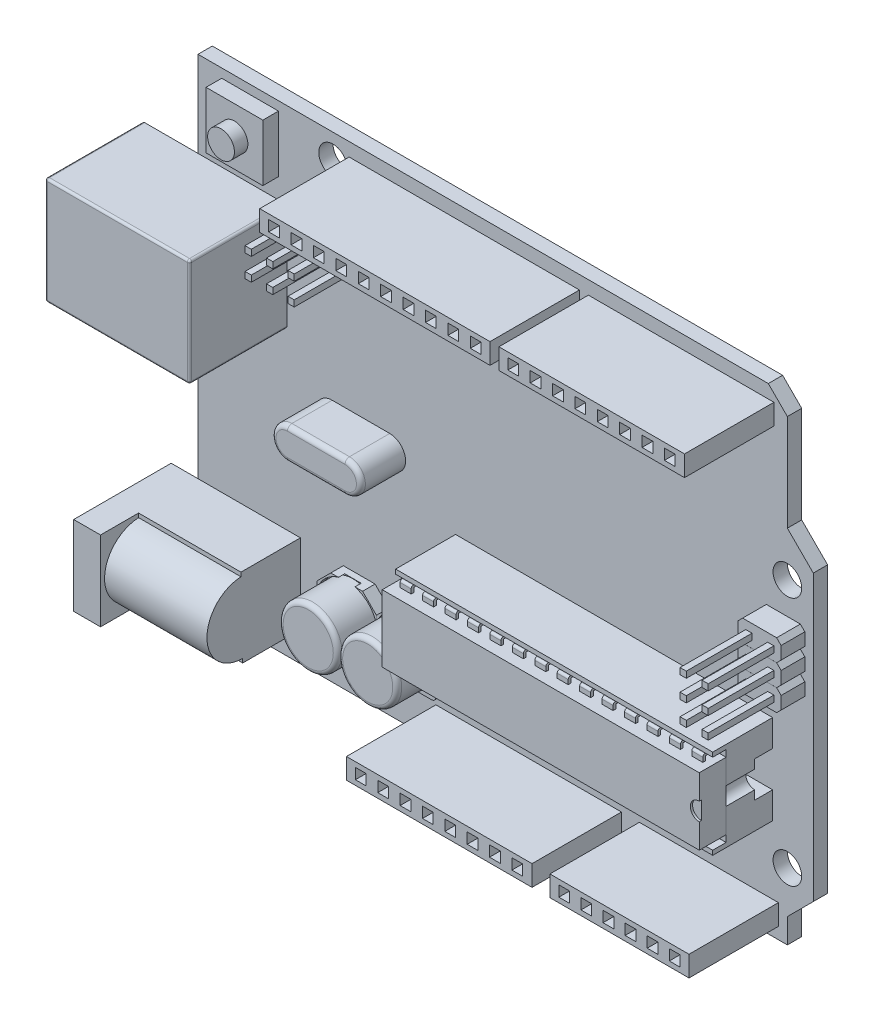
SolidWorks part; units mm, degrees
ref_plane "Plan de face" through (0, 0, 0) normal (0, 0, 1) x (1, 0, 0)
ref_plane "Plan de dessus" through (0, 0, 0) normal (0, 1, 0) x (1, 0, 0)
ref_plane "Plan de droite" through (0, 0, 0) normal (1, 0, 0) x (0, 0, -1)
sketch "Esquisse1" plane through (0, 0, 0) normal (0, 0, 1) x (1, 0, 0)
  line L0 (0, 0) -> (0, 53.3)
  line L1 (0, 53.3) -> (63.7689, 53.3)
  line L2 (63.7689, 53.3) -> (65.9, 51.1689)
  line L3 (68.8, 37.4589) -> (68.8, 5.65)
  line L4 (68.8, 5.65) -> (65.9, 2.75)
  line L5 (65.9, 2.75) -> (65.9, 0)
  line L6 (65.9, 0) -> (0, 0)
  line L7 (65.9, 51.1689) -> (65.9, 40.3589)
  line L8 (65.9, 40.3589) -> (68.8, 37.4589)
  circle A0 centre (14, 2.75) radius 1.6
  circle A1 centre (15.1, 50.55) radius 1.6
  circle A2 centre (65.9, 7.45) radius 1.6
  circle A3 centre (65.9, 35.35) radius 1.6
  dimension "D3" = 3.2
  dimension "D12" = 50.8
  dimension "D7" = 51.9
  dimension "D1" = 53.3
  dimension "D2" = 68.8
  dimension "D4" = 15.2
  dimension "D5" = 14
  dimension "D6" = 2.75
  dimension "D8" = 51.9
  dimension "D9" = 1.1
  dimension "D10" = 4.7
  dimension "D11" = 2.75
  dimension "D13" = 45
  dimension "D14" = 45
  dimension "D16" = 45
extrude "Boss.-Extru.1" add sketch "Esquisse1" along normal blind 1.6
sketch "Esquisse2" plane through (0, 0, 1.6) normal (0, 0, 1) x (1, 0, 0)
  line L0 (-6.2, 43.7) -> (9.95, 43.7)
  line L2 (9.95, 43.7) -> (9.95, 31.7)
  line L3 (9.95, 31.7) -> (-6.2, 31.7)
  line L4 (-6.2, 31.7) -> (-6.2, 43.7)
  line L5 (63.7689, 53.3) -> (0, 53.3) construction
  line L6 (68.8, 5.65) -> (68.8, 37.4589) construction
  dimension "D1" = 9.6
  dimension "D2" = 12
  dimension "D3" = 75
  dimension "D4" = 16.15
extrude "Boss.-Extru.2" add sketch "Esquisse2" along normal blind 10.9 separate body
sketch "Esquisse3" plane through (0, 0, 1.6) normal (0, 0, 1) x (1, 0, 0)
  line L0 (0, 53.3) -> (0, 0) construction
  line L1 (-3, 12.2) -> (11.45, 12.2)
  line L2 (-3, 12.2) -> (-3, 3.3)
  line L3 (-3, 3.3) -> (11.45, 3.3)
  line L4 (11.45, 12.2) -> (11.45, 3.3)
  line L5 (0, 0) -> (65.9, 0) construction
  dimension "D1" = 3
  dimension "D2" = 8.9
  dimension "D3" = 3.3
  dimension "D4" = 14.45
extrude "Boss.-Extru.3" add sketch "Esquisse3" along normal blind 10.9 separate body
sketch "Esquisse4" plane through (0, 0, 1.6) normal (0, 0, 1) x (1, 0, 0)
  line L0 (0, 0) -> (65.9, 0) construction
  line L1 (64.9, 3.6) -> (49.35, 3.6)
  line L2 (64.9, 3.6) -> (64.9, 1.3)
  line L3 (64.9, 1.3) -> (49.35, 1.3)
  line L4 (49.35, 3.6) -> (49.35, 1.3)
  line L5 (50.35, 3.05) -> (51.55, 3.05)
  line L6 (50.35, 3.05) -> (50.35, 1.85)
  line L7 (50.35, 1.85) -> (51.55, 1.85)
  line L8 (51.55, 3.05) -> (51.55, 1.85)
  line L9 (65.9, 0) -> (65.9, 2.75) construction
  line L10 (52.82, 1.85) -> (54.02, 1.85)
  line L11 (54.02, 3.05) -> (54.02, 1.85)
  line L12 (52.82, 3.05) -> (54.02, 3.05)
  line L13 (52.82, 3.05) -> (52.82, 1.85)
  line L14 (55.29, 1.85) -> (56.49, 1.85)
  line L15 (56.49, 3.05) -> (56.49, 1.85)
  line L16 (55.29, 3.05) -> (56.49, 3.05)
  line L17 (55.29, 3.05) -> (55.29, 1.85)
  line L18 (57.76, 1.85) -> (58.96, 1.85)
  line L19 (58.96, 3.05) -> (58.96, 1.85)
  line L20 (57.76, 3.05) -> (58.96, 3.05)
  line L21 (57.76, 3.05) -> (57.76, 1.85)
  line L22 (60.23, 1.85) -> (61.43, 1.85)
  line L23 (61.43, 3.05) -> (61.43, 1.85)
  line L24 (60.23, 3.05) -> (61.43, 3.05)
  line L25 (60.23, 3.05) -> (60.23, 1.85)
  line L26 (62.7, 1.85) -> (63.9, 1.85)
  line L27 (63.9, 3.05) -> (63.9, 1.85)
  line L28 (62.7, 3.05) -> (63.9, 3.05)
  line L29 (62.7, 3.05) -> (62.7, 1.85)
  dimension "D1" = 1
  dimension "D2" = 2.3
  dimension "D3" = 1.3
  dimension "D4" = 1
  dimension "D5" = 1.2
  dimension "D6" = 0.55
  dimension "D7" = 1
  dimension "D9" = 15.55
  dimension "D8" = 6
extrude "Boss.-Extru.4" add sketch "Esquisse4" along normal blind 10 separate body
sketch "Esquisse5" plane through (11.45, 0, 0) normal (1, 0, 0) x (0, 0, -1)
  line L0 (-8.05, 3.7548) -> (-8.05, 3.3)
  line L1 (-12.5, 3.3) -> (-1.6, 3.3) construction
  line L2 (-12.5, 12.2) -> (-1.6, 12.2) construction
  line L3 (-12.5, 12.2) -> (-12.5, 3.3) construction
  line L4 (-8.05, 3.3) -> (-12.5, 3.3)
  line L5 (-12.5, 3.3) -> (-12.5, 12.2)
  line L6 (-12.5, 12.2) -> (-8.2459, 12.2)
  line L7 (-8.2459, 12.2) -> (-8.2459, 11.75)
  arc A0 (-8.2459, 11.75) -> (-8.05, 3.7548) centre (-8.05, 7.7548) ccw
  point P5 (-12.5, 7.75)
  dimension "D1" = 4
  dimension "D2" = 0.45
  dimension "D3" = 4.45
extrude "Enlèv. mat.-Extru.1" cut sketch "Esquisse5" against normal up to surface (11.45 mm away) up to face at (0, 26.65, 0.8)
sketch "Esquisse6" plane through (0, 0, 1.6) normal (0, 0, 1) x (1, 0, 0)
  line L0 (15, 25.525) -> (21.44, 25.525) construction
  line L1 (15, 27.3) -> (21.44, 27.3)
  line L2 (15, 23.75) -> (21.44, 23.75)
  line L4 (-6.2, 31.7) -> (9.95, 31.7) construction
  line L5 (0, 53.3) -> (0, 0) construction
  arc A0 (15, 27.3) -> (15, 23.75) centre (15, 25.525) ccw
  arc A1 (21.44, 23.75) -> (21.44, 27.3) centre (21.44, 25.525) ccw
  point P2 (18.22, 25.525)
  dimension "D1" = 1.775
  dimension "D2" = 6.44
  dimension "D3" = 15
  dimension "D4" = 4.4
extrude "Boss.-Extru.5" add sketch "Esquisse6" along normal blind 5 separate body
sketch "Esquisse8" plane through (0, 0, 1.6) normal (0, 0, 1) x (1, 0, 0)
  line L0 (64.9, 3.6) -> (49.35, 3.6) construction
  line L1 (47.35, 3.6) -> (26.6, 3.6)
  line L2 (47.35, 3.6) -> (47.35, 1.3)
  line L3 (47.35, 1.3) -> (26.6, 1.3)
  line L4 (26.6, 3.6) -> (26.6, 1.3)
  line L5 (49.35, 1.3) -> (64.9, 1.3) construction
  line L6 (49.35, 3.6) -> (49.35, 1.3) construction
  line L7 (51.55, 3.05) -> (50.35, 3.05) construction
  line L8 (27.6, 3.05) -> (28.8, 3.05)
  line L9 (27.6, 3.05) -> (27.6, 1.85)
  line L10 (27.6, 1.85) -> (28.8, 1.85)
  line L11 (28.8, 3.05) -> (28.8, 1.85)
  line L12 (50.35, 1.85) -> (51.55, 1.85) construction
  line L13 (30.1, 1.85) -> (31.3, 1.85)
  line L14 (31.3, 3.05) -> (31.3, 1.85)
  line L15 (30.1, 3.05) -> (31.3, 3.05)
  line L16 (30.1, 3.05) -> (30.1, 1.85)
  line L17 (32.6, 1.85) -> (33.8, 1.85)
  line L18 (33.8, 3.05) -> (33.8, 1.85)
  line L19 (32.6, 3.05) -> (33.8, 3.05)
  line L20 (32.6, 3.05) -> (32.6, 1.85)
  line L21 (35.1, 1.85) -> (36.3, 1.85)
  line L22 (36.3, 3.05) -> (36.3, 1.85)
  line L23 (35.1, 3.05) -> (36.3, 3.05)
  line L24 (35.1, 3.05) -> (35.1, 1.85)
  line L25 (37.6, 1.85) -> (38.8, 1.85)
  line L26 (38.8, 3.05) -> (38.8, 1.85)
  line L27 (37.6, 3.05) -> (38.8, 3.05)
  line L28 (37.6, 3.05) -> (37.6, 1.85)
  line L29 (40.1, 1.85) -> (41.3, 1.85)
  line L30 (41.3, 3.05) -> (41.3, 1.85)
  line L31 (40.1, 3.05) -> (41.3, 3.05)
  line L32 (40.1, 3.05) -> (40.1, 1.85)
  line L33 (42.6, 1.85) -> (43.8, 1.85)
  line L34 (43.8, 3.05) -> (43.8, 1.85)
  line L35 (42.6, 3.05) -> (43.8, 3.05)
  line L36 (42.6, 3.05) -> (42.6, 1.85)
  line L37 (45.1, 1.85) -> (46.3, 1.85)
  line L38 (46.3, 3.05) -> (46.3, 1.85)
  line L39 (45.1, 3.05) -> (46.3, 3.05)
  line L40 (45.1, 3.05) -> (45.1, 1.85)
  point P8 (49.35, 2.45)
  dimension "D1" = 2
  dimension "D2" = 20.75
  dimension "D3" = 1.2
  dimension "D4" = 1
  dimension "D5" = 8
extrude "Boss.-Extru.6" add sketch "Esquisse8" along normal blind 10 separate body
sketch "Esquisse9" plane through (0, 0, 1.6) normal (0, 0, 1) x (1, 0, 0)
  line L0 (14.7, 10.35) -> (14.7, 5.75)
  line L1 (15.2, 5.25) -> (20.85, 5.25)
  line L2 (21.35, 5.75) -> (21.35, 10.35)
  line L3 (21.35, 10.35) -> (19.8, 11.9)
  line L4 (19.8, 11.9) -> (16.25, 11.9)
  line L5 (16.25, 11.9) -> (14.7, 10.35)
  line L6 (11.45, 3.7548) -> (11.45, 11.75) construction
  line L7 (0, 0) -> (65.9, 0) construction
  arc A0 (20.85, 5.25) -> (21.35, 5.75) centre (20.85, 5.75) ccw
  arc A1 (14.7, 5.75) -> (15.2, 5.25) centre (15.2, 5.75) ccw
  dimension "D8" = 0.5
  dimension "D1" = 6.65
  dimension "D2" = 6.65
  dimension "D3" = 45
  dimension "D4" = 45
  dimension "D5" = 3.55
  dimension "D6" = 3.25
  dimension "D7" = 5.25
extrude "Boss.-Extru.7" add sketch "Esquisse9" along normal blind 1.4 separate body
sketch "Esquisse10" plane through (0, 0, 3) normal (0, 0, 1) x (1, 0, 0)
  circle A0 centre (18.025, 8.575) radius 3.45
  dimension "D1" = 6.9
extrude "Enlèv. mat.-Extru.8" cut sketch "Esquisse10" against normal blind 0.7
pattern_linear "Répétition linéaire1" count 2 spacing 6.65 along (1, 0, 0) of bodies 111
sketch "Esquisse11" plane through (0, 0, 2.3) normal (0, 0, 1) x (1, 0, 0)
  circle A0 centre (18.025, 8.575) radius 3.3
  arc A1 (17.1047, 11.9) -> (14.7, 9.4953) centre (18.025, 8.575) ccw construction
  dimension "D1" = 6.6
extrude "Boss.-Extru.8" add sketch "Esquisse11" along normal blind 5 separate body
pattern_linear "Répétition linéaire2" count 2 spacing 6.65 along (1, 0, 0) of "Boss.-Extru.8"
fillet "Congé1" radius 0.5 1 edges at (21.325, 8.575, 7.3)
fillet "Congé2" radius 0.5 1 edges at (27.975, 8.575, 7.3)
fillet "Congé3" radius 0.5 4 edges at (13.225, 25.525, 6.6) (18.22, 27.3, 6.6) (23.215, 25.525, 6.6) (18.22, 23.75, 6.6)
sketch "Esquisse12" plane through (0, 0, 1.6) normal (0, 0, 1) x (1, 0, 0)
  line L0 (63.55, 31.8) -> (67.35, 31.8)
  line L1 (67.35, 31.8) -> (67.85, 31.3)
  line L2 (67.85, 31.3) -> (67.85, 29.8833)
  line L3 (67.85, 29.8833) -> (67.35, 29.3833)
  line L4 (67.35, 29.3833) -> (63.55, 29.3833)
  line L5 (63.55, 29.3833) -> (63.05, 29.8833)
  line L6 (63.05, 29.8833) -> (63.05, 31.3)
  line L7 (63.05, 31.3) -> (63.55, 31.8)
  line L8 (68.8, 5.65) -> (68.8, 37.4589) construction
  line L9 (49.35, 1.3) -> (64.9, 1.3) construction
  dimension "D1" = 45
  dimension "D2" = 45
  dimension "D3" = 45
  dimension "D4" = 2.4167
  dimension "D5" = 4.8
  dimension "D6" = 0.5
  dimension "D7" = 5.75
  dimension "D8" = 30.5
extrude "Boss.-Extru.9" add sketch "Esquisse12" along normal blind 2.65 separate body
pattern_linear "Répétition linéaire3" count 3 spacing 2.42 along (0, -1, 0) of bodies 115
sketch "Esquisse13" plane through (0, 0, 1.6) normal (0, 0, 1) x (1, 0, 0)
  line L0 (14.4, 43.9) -> (14.4, 47.7)
  line L1 (14.4, 47.7) -> (14.9, 48.2)
  line L2 (14.9, 48.2) -> (16.3167, 48.2)
  line L3 (16.3167, 48.2) -> (16.8167, 47.7)
  line L4 (16.8167, 47.7) -> (16.8167, 43.9)
  line L5 (16.8167, 43.9) -> (16.3167, 43.4)
  line L6 (16.3167, 43.4) -> (14.9, 43.4)
  line L7 (14.9, 43.4) -> (14.4, 43.9)
  line L8 (65.9, 40.3589) -> (65.9, 51.1689) construction
  line L9 (63.7689, 53.3) -> (0, 53.3) construction
  dimension "D1" = 45
  dimension "D2" = 45
  dimension "D3" = 45
  dimension "D4" = 2.4167
  dimension "D5" = 4.8
  dimension "D6" = 0.5
  dimension "D7" = 51.5
  dimension "D8" = 9.9
extrude "Boss.-Extru.10" add sketch "Esquisse13" along normal up to surface (2.65 mm away) up to face at (65.45, 30.5917, 4.25)
pattern_linear "Répétition linéaire4" count 3 spacing 2.42 along (1, 0, 0) of "Boss.-Extru.10"
sketch "Esquisse14" plane through (0, 0, 1.6) normal (0, 0, 1) x (1, 0, 0)
  line L0 (63.7689, 53.3) -> (0, 53.3) construction
  line L1 (2.65, 52.3) -> (9, 52.3)
  line L2 (2.65, 52.3) -> (2.65, 45.95)
  line L3 (2.65, 45.95) -> (9, 45.95)
  line L4 (9, 52.3) -> (9, 45.95)
  line L5 (0, 53.3) -> (0, 0) construction
  dimension "D1" = 6.35
  dimension "D2" = 6.35
  dimension "D3" = 1
  dimension "D4" = 9
extrude "Boss.-Extru.11" add sketch "Esquisse14" along normal blind 1.75 separate body
sketch "Esquisse15" plane through (0, 0, 3.35) normal (0, 0, 1) x (1, 0, 0)
  circle A0 centre (5.825, 49.125) radius 1.5
  point P2 (5.825, 49.125)
  dimension "D1" = 3
extrude "Boss.-Extru.12" add sketch "Esquisse15" along normal blind 1.5 separate body
sketch "Esquisse16" plane through (0, 0, 4.25) normal (0, 0, 1) x (1, 0, 0)
  line L0 (63.05, 26.46) -> (63.05, 25.0433) construction
  line L1 (67.05, 25.4) -> (66.35, 25.4)
  line L2 (67.05, 25.4) -> (67.05, 26.1)
  line L3 (67.05, 26.1) -> (66.35, 26.1)
  line L4 (66.35, 25.4) -> (66.35, 26.1)
  line L6 (67.35, 26.96) -> (63.55, 26.96) construction
  line L9 (64.6, 25.4) -> (63.9, 25.4)
  line L10 (64.6, 25.4) -> (64.6, 26.1)
  line L11 (64.6, 26.1) -> (63.9, 26.1)
  line L12 (63.9, 25.4) -> (63.9, 26.1)
  line L13 (64.6, 27.7833) -> (63.9, 27.7833)
  line L14 (64.6, 27.7833) -> (64.6, 28.4833)
  line L15 (64.6, 28.4833) -> (63.9, 28.4833)
  line L16 (63.9, 27.7833) -> (63.9, 28.4833)
  line L17 (64.6, 30.1667) -> (63.9, 30.1667)
  line L18 (64.6, 30.1667) -> (64.6, 30.8667)
  line L19 (64.6, 30.8667) -> (63.9, 30.8667)
  line L20 (63.9, 30.1667) -> (63.9, 30.8667)
  line L21 (67.05, 27.7833) -> (66.35, 27.7833)
  line L22 (67.05, 27.7833) -> (67.05, 28.4833)
  line L23 (67.05, 28.4833) -> (66.35, 28.4833)
  line L24 (66.35, 27.7833) -> (66.35, 28.4833)
  line L25 (67.05, 30.1667) -> (66.35, 30.1667)
  line L26 (67.05, 30.1667) -> (67.05, 30.8667)
  line L27 (67.05, 30.8667) -> (66.35, 30.8667)
  line L28 (66.35, 30.1667) -> (66.35, 30.8667)
  dimension "D1" = 0.7
  dimension "D2" = 4
  dimension "D3" = 0.86
  dimension "D4" = 2
  dimension "D5" = 3
extrude "Boss.-Extru.13" add sketch "Esquisse16" along normal up to surface (7.35 mm away) separate body up to face at (60.83, 2.45, 11.6)
sketch "Esquisse17" plane through (0, 0, 4.25) normal (0, 0, 1) x (1, 0, 0)
  line L0 (14.4, 43.9) -> (14.4, 47.7) construction
  line L1 (15.96, 44.2) -> (15.26, 44.2)
  line L2 (15.96, 44.2) -> (15.96, 44.9)
  line L3 (15.96, 44.9) -> (15.26, 44.9)
  line L4 (15.26, 44.2) -> (15.26, 44.9)
  line L6 (14.9, 43.4) -> (16.3167, 43.4) construction
  line L9 (16.3167, 48.2) -> (14.9, 48.2) construction
  line L10 (15.96, 46.7) -> (15.26, 46.7)
  line L11 (15.96, 46.7) -> (15.96, 47.4)
  line L12 (15.96, 47.4) -> (15.26, 47.4)
  line L13 (15.26, 46.7) -> (15.26, 47.4)
  line L14 (18.36, 46.7) -> (17.66, 46.7)
  line L15 (18.36, 46.7) -> (18.36, 47.4)
  line L16 (18.36, 47.4) -> (17.66, 47.4)
  line L17 (17.66, 46.7) -> (17.66, 47.4)
  line L18 (18.36, 44.2) -> (17.66, 44.2)
  line L19 (18.36, 44.2) -> (18.36, 44.9)
  line L20 (18.36, 44.9) -> (17.66, 44.9)
  line L21 (17.66, 44.2) -> (17.66, 44.9)
  line L22 (20.76, 46.7) -> (20.06, 46.7)
  line L23 (20.76, 46.7) -> (20.76, 47.4)
  line L24 (20.76, 47.4) -> (20.06, 47.4)
  line L25 (20.06, 46.7) -> (20.06, 47.4)
  line L26 (20.76, 44.2) -> (20.06, 44.2)
  line L27 (20.76, 44.2) -> (20.76, 44.9)
  line L28 (20.76, 44.9) -> (20.06, 44.9)
  line L29 (20.06, 44.2) -> (20.06, 44.9)
  point P21 (35.61, 45.8)
  dimension "D1" = 0.7
  dimension "D2" = 0.86
  dimension "D3" = 0.8
  dimension "D4" = 0.8
  dimension "D5" = 0.7
  dimension "D6" = 3
extrude "Boss.-Extru.14" add sketch "Esquisse17" along normal up to surface (7.35 mm away) separate body up to face at (43.2, 2.45, 11.6)
sketch "Esquisse19" plane through (0, 0, 1.6) normal (0, 0, 1) x (1, 0, 0)
  line L0 (64.4, 51.8) -> (43.65, 51.8)
  line L1 (64.4, 51.8) -> (64.4, 49.5)
  line L2 (64.4, 49.5) -> (43.65, 49.5)
  line L3 (43.65, 51.8) -> (43.65, 49.5)
  line L4 (44.65, 51.25) -> (45.85, 51.25)
  line L5 (44.65, 51.25) -> (44.65, 50.05)
  line L6 (44.65, 50.05) -> (45.85, 50.05)
  line L7 (45.85, 51.25) -> (45.85, 50.05)
  line L8 (47.15, 50.05) -> (48.35, 50.05)
  line L9 (48.35, 51.25) -> (48.35, 50.05)
  line L10 (47.15, 51.25) -> (48.35, 51.25)
  line L11 (47.15, 51.25) -> (47.15, 50.05)
  line L12 (49.65, 50.05) -> (50.85, 50.05)
  line L13 (50.85, 51.25) -> (50.85, 50.05)
  line L14 (49.65, 51.25) -> (50.85, 51.25)
  line L15 (49.65, 51.25) -> (49.65, 50.05)
  line L16 (52.15, 50.05) -> (53.35, 50.05)
  line L17 (53.35, 51.25) -> (53.35, 50.05)
  line L18 (52.15, 51.25) -> (53.35, 51.25)
  line L19 (52.15, 51.25) -> (52.15, 50.05)
  line L20 (54.65, 50.05) -> (55.85, 50.05)
  line L21 (55.85, 51.25) -> (55.85, 50.05)
  line L22 (54.65, 51.25) -> (55.85, 51.25)
  line L23 (54.65, 51.25) -> (54.65, 50.05)
  line L24 (57.15, 50.05) -> (58.35, 50.05)
  line L25 (58.35, 51.25) -> (58.35, 50.05)
  line L26 (57.15, 51.25) -> (58.35, 51.25)
  line L27 (57.15, 51.25) -> (57.15, 50.05)
  line L28 (59.65, 50.05) -> (60.85, 50.05)
  line L29 (60.85, 51.25) -> (60.85, 50.05)
  line L30 (59.65, 51.25) -> (60.85, 51.25)
  line L31 (59.65, 51.25) -> (59.65, 50.05)
  line L32 (62.15, 50.05) -> (63.35, 50.05)
  line L33 (63.35, 51.25) -> (63.35, 50.05)
  line L34 (62.15, 51.25) -> (63.35, 51.25)
  line L35 (62.15, 51.25) -> (62.15, 50.05)
  line L37 (65.9, 40.3589) -> (65.9, 51.1689) construction
  line L38 (63.7689, 53.3) -> (0, 53.3) construction
  dimension "D1" = 20.75
  dimension "D2" = 1.2
  dimension "D3" = 1
  dimension "D4" = 2.3
  dimension "D5" = 0.55
  dimension "D6" = 0.55
  dimension "D7" = 1.2
  dimension "D8" = 1.3
  dimension "D9" = 1.3
  dimension "D10" = 1.3
  dimension "D11" = 1.3
  dimension "D12" = 1.3
  dimension "D13" = 1.3
  dimension "D14" = 1.3
  dimension "D15" = 1.05
  dimension "D16" = 1.2
  dimension "D17" = 1.2
  dimension "D18" = 1.2
  dimension "D19" = 1.2
  dimension "D20" = 1.2
  dimension "D21" = 1.2
  dimension "D22" = 1.5
  dimension "D23" = 1.5
extrude "Boss.-Extru.15" add sketch "Esquisse19" along normal blind 10 separate body
sketch "Esquisse20" plane through (0, 0, 1.6) normal (0, 0, 1) x (1, 0, 0)
  line L0 (43.65, 49.5) -> (64.4, 49.5) construction
  line L1 (42.65, 49.5) -> (16.9, 49.5)
  line L2 (42.65, 49.5) -> (42.65, 51.8)
  line L3 (42.65, 51.8) -> (16.9, 51.8)
  line L4 (16.9, 49.5) -> (16.9, 51.8)
  line L5 (64.4, 51.8) -> (43.65, 51.8) construction
  line L6 (43.65, 51.8) -> (43.65, 49.5) construction
  line L7 (45.85, 51.25) -> (44.65, 51.25) construction
  line L8 (41.65, 50.05) -> (40.45, 50.05)
  line L9 (41.65, 50.05) -> (41.65, 51.25)
  line L10 (41.65, 51.25) -> (40.45, 51.25)
  line L11 (40.45, 50.05) -> (40.45, 51.25)
  line L12 (44.65, 50.05) -> (45.85, 50.05) construction
  line L13 (39.1444, 50.05) -> (37.9444, 50.05)
  line L14 (37.9444, 50.05) -> (37.9444, 51.25)
  line L15 (39.1444, 51.25) -> (37.9444, 51.25)
  line L16 (39.1444, 50.05) -> (39.1444, 51.25)
  line L17 (36.6389, 50.05) -> (35.4389, 50.05)
  line L18 (35.4389, 50.05) -> (35.4389, 51.25)
  line L19 (36.6389, 51.25) -> (35.4389, 51.25)
  line L20 (36.6389, 50.05) -> (36.6389, 51.25)
  line L21 (34.1333, 50.05) -> (32.9333, 50.05)
  line L22 (32.9333, 50.05) -> (32.9333, 51.25)
  line L23 (34.1333, 51.25) -> (32.9333, 51.25)
  line L24 (34.1333, 50.05) -> (34.1333, 51.25)
  line L25 (31.6278, 50.05) -> (30.4278, 50.05)
  line L26 (30.4278, 50.05) -> (30.4278, 51.25)
  line L27 (31.6278, 51.25) -> (30.4278, 51.25)
  line L28 (31.6278, 50.05) -> (31.6278, 51.25)
  line L29 (29.1222, 50.05) -> (27.9222, 50.05)
  line L30 (27.9222, 50.05) -> (27.9222, 51.25)
  line L31 (29.1222, 51.25) -> (27.9222, 51.25)
  line L32 (29.1222, 50.05) -> (29.1222, 51.25)
  line L33 (26.6167, 50.05) -> (25.4167, 50.05)
  line L34 (25.4167, 50.05) -> (25.4167, 51.25)
  line L35 (26.6167, 51.25) -> (25.4167, 51.25)
  line L36 (26.6167, 50.05) -> (26.6167, 51.25)
  line L37 (24.1111, 50.05) -> (22.9111, 50.05)
  line L38 (22.9111, 50.05) -> (22.9111, 51.25)
  line L39 (24.1111, 51.25) -> (22.9111, 51.25)
  line L40 (24.1111, 50.05) -> (24.1111, 51.25)
  line L41 (21.6056, 50.05) -> (20.4056, 50.05)
  line L42 (20.4056, 50.05) -> (20.4056, 51.25)
  line L43 (21.6056, 51.25) -> (20.4056, 51.25)
  line L44 (21.6056, 50.05) -> (21.6056, 51.25)
  line L45 (19.1, 50.05) -> (17.9, 50.05)
  line L46 (17.9, 50.05) -> (17.9, 51.25)
  line L47 (19.1, 51.25) -> (17.9, 51.25)
  line L48 (19.1, 50.05) -> (19.1, 51.25)
  dimension "D1" = 25.75
  dimension "D2" = 1
  dimension "D3" = 1.2
  dimension "D4" = 1
  dimension "D6" = 1
  dimension "D5" = 10
extrude "Boss.-Extru.16" add sketch "Esquisse20" along normal blind 10 separate body
sketch "Esquisse21" plane through (0, 0, 1.6) normal (0, 0, 1) x (1, 0, 0)
  line L0 (49.35, 1.3) -> (64.9, 1.3) construction
  line L1 (64.25, 11.2) -> (28.8, 11.2)
  line L2 (64.25, 11.2) -> (64.25, 15.2)
  line L3 (64.25, 21.2) -> (28.8, 21.2)
  line L4 (28.8, 11.2) -> (28.8, 21.2)
  line L5 (68.8, 5.65) -> (68.8, 37.4589) construction
  line L7 (64.25, 17.2) -> (64.25, 21.2)
  arc A0 (64.25, 15.2) -> (64.25, 17.2) centre (64.25, 16.2) cw
  dimension "D6" = 1
  dimension "D1" = 35.45
  dimension "D2" = 10
  dimension "D3" = 19.9
  dimension "D4" = 40
  dimension "D5" = 5
extrude "Boss.-Extru.17" add sketch "Esquisse21" along normal blind 6.7 separate body
sketch "Esquisse22" plane through (64.25, 0, 0) normal (1, 0, 0) x (0, 0, -1)
  line L0 (-1.6, 17.2) -> (-1.6, 21.2) construction
  line L1 (-3.6, 14.2) -> (-1.6, 14.2)
  line L2 (-3.6, 14.2) -> (-3.6, 18.2)
  line L3 (-3.6, 18.2) -> (-1.6, 18.2)
  line L4 (-1.6, 14.2) -> (-1.6, 18.2)
  line L5 (-8.3, 11.2) -> (-1.6, 11.2) construction
  line L6 (-8.3, 21.2) -> (-1.6, 21.2) construction
  line L7 (-8.3, 11.2) -> (-8.3, 15.2) construction
  line L8 (-8.3, 11.7) -> (-6.8, 11.7)
  line L9 (-8.3, 11.7) -> (-8.3, 20.7)
  line L10 (-8.3, 20.7) -> (-6.8, 20.7)
  line L11 (-6.8, 11.7) -> (-6.8, 20.7)
  dimension "D1" = 3
  dimension "D2" = 3
  dimension "D3" = 2
  dimension "D4" = 1.5
  dimension "D5" = 0.5
  dimension "D6" = 0.5
extrude "Enlèv. mat.-Extru.9" cut sketch "Esquisse22" against normal up to next
sketch "Esquisse23" plane through (0, 0, 6.8) normal (0, 0, 1) x (1, 0, 0)
  line L0 (28.8, 20.7) -> (28.8, 11.7) construction
  line L1 (28.8, 12.45) -> (64.25, 12.45)
  line L2 (28.8, 12.45) -> (28.8, 19.95)
  line L3 (28.8, 19.95) -> (64.25, 19.95)
  line L4 (64.25, 12.45) -> (64.25, 19.95)
  line L5 (64.25, 17.2) -> (64.25, 20.7) construction
  line L6 (28.8, 20.7) -> (64.25, 20.7) construction
  dimension "D1" = 0.75
  dimension "7.5" = 7.5
extrude "Boss.-Extru.18" add sketch "Esquisse23" along normal blind 3 separate body
sketch "Esquisse24" plane through (0, 0, 9.8) normal (0, 0, 1) x (1, 0, 0)
  line L0 (64.25, 19.95) -> (28.8, 19.95) construction
  line L1 (29.6, 19.95) -> (30.8322, 19.95)
  line L2 (29.6, 19.95) -> (29.6, 20.7)
  line L3 (29.6, 20.7) -> (30.8322, 20.7)
  line L4 (30.8322, 19.95) -> (30.8322, 20.7)
  line L5 (28.8, 20.7) -> (64.25, 20.7) construction
  line L6 (32.1091, 19.95) -> (33.3412, 19.95)
  line L7 (32.1091, 20.7) -> (33.3412, 20.7)
  line L8 (33.3412, 19.95) -> (33.3412, 20.7)
  line L9 (32.1091, 19.95) -> (32.1091, 20.7)
  line L10 (34.6181, 19.95) -> (35.8503, 19.95)
  line L11 (34.6181, 20.7) -> (35.8503, 20.7)
  line L12 (35.8503, 19.95) -> (35.8503, 20.7)
  line L13 (34.6181, 19.95) -> (34.6181, 20.7)
  line L14 (37.1272, 19.95) -> (38.3593, 19.95)
  line L15 (37.1272, 20.7) -> (38.3593, 20.7)
  line L16 (38.3593, 19.95) -> (38.3593, 20.7)
  line L17 (37.1272, 19.95) -> (37.1272, 20.7)
  line L18 (39.6363, 19.95) -> (40.8684, 19.95)
  line L19 (39.6363, 20.7) -> (40.8684, 20.7)
  line L20 (40.8684, 19.95) -> (40.8684, 20.7)
  line L21 (39.6363, 19.95) -> (39.6363, 20.7)
  line L22 (42.1453, 19.95) -> (43.3775, 19.95)
  line L23 (42.1453, 20.7) -> (43.3775, 20.7)
  line L24 (43.3775, 19.95) -> (43.3775, 20.7)
  line L25 (42.1453, 19.95) -> (42.1453, 20.7)
  line L26 (44.6544, 19.95) -> (45.8865, 19.95)
  line L27 (44.6544, 20.7) -> (45.8865, 20.7)
  line L28 (45.8865, 19.95) -> (45.8865, 20.7)
  line L29 (44.6544, 19.95) -> (44.6544, 20.7)
  line L30 (47.1635, 19.95) -> (48.3956, 19.95)
  line L31 (47.1635, 20.7) -> (48.3956, 20.7)
  line L32 (48.3956, 19.95) -> (48.3956, 20.7)
  line L33 (47.1635, 19.95) -> (47.1635, 20.7)
  line L34 (49.6725, 19.95) -> (50.9047, 19.95)
  line L35 (49.6725, 20.7) -> (50.9047, 20.7)
  line L36 (50.9047, 19.95) -> (50.9047, 20.7)
  line L37 (49.6725, 19.95) -> (49.6725, 20.7)
  line L38 (52.1816, 19.95) -> (53.4137, 19.95)
  line L39 (52.1816, 20.7) -> (53.4137, 20.7)
  line L40 (53.4137, 19.95) -> (53.4137, 20.7)
  line L41 (52.1816, 19.95) -> (52.1816, 20.7)
  line L42 (54.6907, 19.95) -> (55.9228, 19.95)
  line L43 (54.6907, 20.7) -> (55.9228, 20.7)
  line L44 (55.9228, 19.95) -> (55.9228, 20.7)
  line L45 (54.6907, 19.95) -> (54.6907, 20.7)
  line L46 (57.1997, 19.95) -> (58.4319, 19.95)
  line L47 (57.1997, 20.7) -> (58.4319, 20.7)
  line L48 (58.4319, 19.95) -> (58.4319, 20.7)
  line L49 (57.1997, 19.95) -> (57.1997, 20.7)
  line L50 (59.7088, 19.95) -> (60.9409, 19.95)
  line L51 (59.7088, 20.7) -> (60.9409, 20.7)
  line L52 (60.9409, 19.95) -> (60.9409, 20.7)
  line L53 (59.7088, 19.95) -> (59.7088, 20.7)
  line L54 (62.2178, 19.95) -> (63.45, 19.95)
  line L55 (62.2178, 20.7) -> (63.45, 20.7)
  line L56 (63.45, 19.95) -> (63.45, 20.7)
  line L57 (62.2178, 19.95) -> (62.2178, 20.7)
  line L58 (32.1091, 11.7) -> (33.3412, 11.7)
  line L59 (32.1091, 12.45) -> (33.3412, 12.45)
  line L60 (33.3412, 11.7) -> (33.3412, 12.45)
  line L61 (32.1091, 11.7) -> (32.1091, 12.45)
  line L62 (34.6181, 11.7) -> (35.8503, 11.7)
  line L63 (34.6181, 12.45) -> (35.8503, 12.45)
  line L64 (35.8503, 11.7) -> (35.8503, 12.45)
  line L65 (34.6181, 11.7) -> (34.6181, 12.45)
  line L66 (37.1272, 11.7) -> (38.3593, 11.7)
  line L67 (37.1272, 12.45) -> (38.3593, 12.45)
  line L68 (38.3593, 11.7) -> (38.3593, 12.45)
  line L69 (37.1272, 11.7) -> (37.1272, 12.45)
  line L70 (39.6363, 11.7) -> (40.8684, 11.7)
  line L71 (39.6363, 12.45) -> (40.8684, 12.45)
  line L72 (40.8684, 11.7) -> (40.8684, 12.45)
  line L73 (39.6363, 11.7) -> (39.6363, 12.45)
  line L74 (42.1453, 11.7) -> (43.3775, 11.7)
  line L75 (42.1453, 12.45) -> (43.3775, 12.45)
  line L76 (43.3775, 11.7) -> (43.3775, 12.45)
  line L77 (42.1453, 11.7) -> (42.1453, 12.45)
  line L78 (44.6544, 11.7) -> (45.8865, 11.7)
  line L79 (44.6544, 12.45) -> (45.8865, 12.45)
  line L80 (45.8865, 11.7) -> (45.8865, 12.45)
  line L81 (44.6544, 11.7) -> (44.6544, 12.45)
  line L82 (47.1635, 11.7) -> (48.3956, 11.7)
  line L83 (47.1635, 12.45) -> (48.3956, 12.45)
  line L84 (48.3956, 11.7) -> (48.3956, 12.45)
  line L85 (47.1635, 11.7) -> (47.1635, 12.45)
  line L86 (49.6725, 11.7) -> (50.9047, 11.7)
  line L87 (49.6725, 12.45) -> (50.9047, 12.45)
  line L88 (50.9047, 11.7) -> (50.9047, 12.45)
  line L89 (49.6725, 11.7) -> (49.6725, 12.45)
  line L90 (52.1816, 11.7) -> (53.4137, 11.7)
  line L91 (52.1816, 12.45) -> (53.4137, 12.45)
  line L92 (53.4137, 11.7) -> (53.4137, 12.45)
  line L93 (52.1816, 11.7) -> (52.1816, 12.45)
  line L94 (54.6907, 11.7) -> (55.9228, 11.7)
  line L95 (54.6907, 12.45) -> (55.9228, 12.45)
  line L96 (55.9228, 11.7) -> (55.9228, 12.45)
  line L97 (54.6907, 11.7) -> (54.6907, 12.45)
  line L98 (57.1997, 11.7) -> (58.4319, 11.7)
  line L99 (57.1997, 12.45) -> (58.4319, 12.45)
  line L100 (58.4319, 11.7) -> (58.4319, 12.45)
  line L101 (57.1997, 11.7) -> (57.1997, 12.45)
  line L102 (59.7088, 11.7) -> (60.9409, 11.7)
  line L103 (59.7088, 12.45) -> (60.9409, 12.45)
  line L104 (60.9409, 11.7) -> (60.9409, 12.45)
  line L105 (59.7088, 11.7) -> (59.7088, 12.45)
  line L106 (62.2178, 11.7) -> (63.45, 11.7)
  line L107 (62.2178, 12.45) -> (63.45, 12.45)
  line L108 (63.45, 11.7) -> (63.45, 12.45)
  line L109 (62.2178, 11.7) -> (62.2178, 12.45)
  line L110 (29.6, 11.7) -> (30.8322, 11.7)
  line L111 (29.6, 12.45) -> (30.8322, 12.45)
  line L112 (30.8322, 11.7) -> (30.8322, 12.45)
  line L113 (29.6, 11.7) -> (29.6, 12.45)
  line L114 (28.8, 19.95) -> (28.8, 12.45) construction
  line L115 (64.25, 17.2) -> (64.25, 20.7) construction
  dimension "D3" = 0.8
  dimension "D4" = 0.8
  dimension "D1" = 14
  dimension "D2" = 2
extrude "Boss.-Extru.19" add sketch "Esquisse24" against normal blind 1.8 from offset 1.2 separate body offset against normal yes
fillet "Congé4" radius 0.25 1 edges at (30.2161, 11.7, 8.6)
fillet "Congé5" radius 0.25 1 edges at (32.7251, 11.7, 8.6)
fillet "Congé6" radius 0.25 1 edges at (35.2342, 11.7, 8.6)
fillet "Congé7" radius 0.25 1 edges at (37.7433, 11.7, 8.6)
fillet "Congé8" radius 0.25 1 edges at (40.2523, 11.7, 8.6)
fillet "Congé9" radius 0.25 1 edges at (42.7614, 11.7, 8.6)
fillet "Congé10" radius 0.25 1 edges at (45.2705, 11.7, 8.6)
fillet "Congé11" radius 0.25 1 edges at (47.7795, 11.7, 8.6)
fillet "Congé12" radius 0.25 1 edges at (50.2886, 11.7, 8.6)
fillet "Congé13" radius 0.25 1 edges at (52.7977, 11.7, 8.6)
fillet "Congé14" radius 0.25 1 edges at (55.3067, 11.7, 8.6)
fillet "Congé15" radius 0.25 1 edges at (57.8158, 11.7, 8.6)
fillet "Congé16" radius 0.25 1 edges at (30.2161, 20.7, 8.6)
fillet "Congé17" radius 0.25 1 edges at (32.7251, 20.7, 8.6)
fillet "Congé18" radius 0.25 1 edges at (37.7433, 20.7, 8.6)
fillet "Congé19" radius 0.25 1 edges at (35.2342, 20.7, 8.6)
fillet "Congé20" radius 0.25 1 edges at (40.2523, 20.7, 8.6)
fillet "Congé21" radius 0.25 1 edges at (42.7614, 20.7, 8.6)
fillet "Congé22" radius 0.25 1 edges at (47.7795, 20.7, 8.6)
fillet "Congé23" radius 0.25 1 edges at (50.2886, 20.7, 8.6)
fillet "Congé24" radius 0.25 1 edges at (52.7977, 20.7, 8.6)
fillet "Congé25" radius 0.25 1 edges at (55.3067, 20.7, 8.6)
fillet "Congé26" radius 0.25 1 edges at (57.8158, 20.7, 8.6)
fillet "Congé27" radius 0.25 1 edges at (60.3249, 20.7, 8.6)
fillet "Congé28" radius 0.25 1 edges at (62.8339, 20.7, 8.6)
fillet "Congé29" radius 0.25 8 edges at (-6.2, 43.7, 7.05) (-6.2, 37.7, 12.5) (-6.2, 31.7, 7.05) (1.875, 43.7, 12.5) (9.95, 43.7, 7.05) (9.95, 31.7, 7.05) (9.95, 37.7, 12.5) (1.875, 31.7, 12.5)
sketch "Esquisse25" plane through (-3, 0, 0) normal (-1, 0, 0) x (0, 0, 1)
  line L0 (1.6, 12.2) -> (1.6, 3.3) construction
  line L1 (12.5, 3.3) -> (1.6, 3.3) construction
  circle A0 centre (8.1, 7.8) radius 3.05
  circle A1 centre (8.1, 7.8) radius 1
  dimension "D1" = 6.1
  dimension "D2" = 2
  dimension "D3" = 6.5
  dimension "D4" = 4.5
extrude "Enlèv. mat.-Extru.10" cut sketch "Esquisse25" against normal blind 11
fillet "Congé30" radius 1 1 edges at (-3, 6.8, 8.1)
sketch "Esquisse26" plane through (-6.2, 0, 0) normal (-1, 0, 0) x (0, 0, 1)
  line L0 (9.55, 41.9479) -> (3.75, 41.9479)
  line L1 (3.75, 41.9479) -> (3.75, 33.4479)
  line L2 (3.75, 33.4479) -> (9.55, 33.4479)
  line L3 (9.55, 33.4479) -> (11.3, 35.1979)
  line L4 (11.3, 35.1979) -> (11.3, 40.1979)
  line L5 (11.3, 40.1979) -> (9.55, 41.9479)
  line L6 (12.5, 43.45) -> (12.5, 31.95) construction
  line L8 (1.6, 43.7) -> (12.25, 43.7) construction
  line L10 (8.95, 40.3229) -> (5.95, 40.3229)
  line L11 (8.95, 40.3229) -> (8.95, 35.0729)
  line L12 (8.95, 35.0729) -> (5.95, 35.0729)
  line L13 (5.95, 40.3229) -> (5.95, 35.0729)
  dimension "D1" = 8.5
  dimension "D2" = 5
  dimension "D3" = 45
  dimension "D4" = 45
  dimension "D5" = 1.2
  dimension "D6" = 1.7521
  dimension "D7" = 5.8
  dimension "D8" = 3
  dimension "D9" = 5.25
  dimension "D10" = 1.625
  dimension "D11" = 2.2
extrude "Enlèv. mat.-Extru.11" cut sketch "Esquisse26" against normal blind 10.15
sketch "Esquisse27" plane through (63.45, 0, 0) normal (1, 0, 0) x (0, 0, -1)
  line L0 (-9.8, 12.45) -> (-6.8, 12.45) construction
  line L1 (-8.3, 12.45) -> (-6.8, 12.45)
  line L2 (-8.3, 12.45) -> (-8.3, 11.95)
  line L3 (-8.3, 11.95) -> (-6.8, 11.95)
  line L4 (-6.8, 12.45) -> (-6.8, 11.95)
  line L5 (-6.8, 11.7) -> (-6.8, 12.45) construction
  line L6 (-9.8, 19.95) -> (-6.8, 19.95) construction
  line L7 (-8.3, 19.95) -> (-6.8, 19.95)
  line L8 (-8.3, 19.95) -> (-8.3, 20.45)
  line L9 (-8.3, 20.45) -> (-6.8, 20.45)
  line L10 (-6.8, 19.95) -> (-6.8, 20.45)
  line L11 (-6.8, 17.2) -> (-6.8, 20.7) construction
  dimension "D1" = 0.5
  dimension "D2" = 0.5
extrude "Enlèv. mat.-Extru.12" cut sketch "Esquisse27" against normal up to surface (34.65 mm away)
fillet "Congé31" radius 0.25 1 edges at (45.2705, 20.7, 8.6)
fillet "Congé32" radius 0.25 1 edges at (62.8339, 11.7, 8.6)
fillet "Congé33" radius 0.25 1 edges at (60.3249, 11.7, 8.6)
sketch "Esquisse28" plane through (0, 0, 9.8) normal (0, 0, 1) x (1, 0, 0)
  line L0 (64.25, 12.45) -> (64.25, 19.95) construction
  circle A0 centre (64.25, 16.2) radius 1
  dimension "D1" = 2
extrude "Enlèv. mat.-Extru.13" cut sketch "Esquisse28" against normal blind 0.25
sketch "Esquisse29" plane through (0, 3.3, 0) normal (0, -1, 0) x (1, 0, 0)
  line L0 (-3, 1.6) -> (11.45, 1.6) construction
  line L1 (6.95, 5.5) -> (9.95, 5.5)
  line L2 (6.95, 5.5) -> (6.95, 1.6)
  line L3 (6.95, 1.6) -> (9.95, 1.6)
  line L4 (9.95, 5.5) -> (9.95, 1.6)
  line L5 (11.45, 8.05) -> (11.45, 1.6) construction
  dimension "D1" = 3
  dimension "D2" = 3.9
  dimension "D3" = 1.5
extrude "Boss.-Extru.20" add sketch "Esquisse29" along normal blind 0.25 separate body
fillet "Congé34" radius 0.25 1 edges at (8.45, 3.05, 5.5)
sketch "Esquisse30" plane through (-6.2, 0, 0) normal (-1, 0, 0) x (0, 0, 1)
  line L0 (8.95, 35.0729) -> (8.95, 40.3229) construction
  line L1 (8.95, 39.3229) -> (9.25, 39.3229)
  line L2 (8.95, 39.3229) -> (8.95, 38.6229)
  line L3 (8.95, 38.6229) -> (9.25, 38.6229)
  line L4 (9.25, 39.3229) -> (9.25, 38.6229)
  line L5 (8.95, 35.0729) -> (8.95, 40.3229) construction
  line L6 (9.25, 36.7729) -> (8.95, 36.7729)
  line L7 (9.25, 36.7729) -> (9.25, 36.0729)
  line L8 (9.25, 36.0729) -> (8.95, 36.0729)
  line L9 (8.95, 36.7729) -> (8.95, 36.0729)
  line L10 (8.95, 40.3229) -> (5.95, 40.3229) construction
  line L11 (5.95, 35.0729) -> (8.95, 35.0729) construction
  line L12 (7.45, 41.382) -> (7.45, 33.7549) construction
  line L13 (5.95, 40.3229) -> (5.95, 35.0729) construction
  line L14 (5.65, 36.7729) -> (5.95, 36.7729)
  line L15 (5.95, 36.7729) -> (5.95, 36.0729)
  line L16 (5.65, 36.0729) -> (5.95, 36.0729)
  line L17 (5.65, 36.7729) -> (5.65, 36.0729)
  line L18 (5.95, 39.3229) -> (5.95, 38.6229)
  line L19 (5.95, 38.6229) -> (5.65, 38.6229)
  line L20 (5.95, 39.3229) -> (5.65, 39.3229)
  line L21 (5.65, 39.3229) -> (5.65, 38.6229)
  dimension "D1" = 0.3
  dimension "D2" = 0.7
  dimension "D3" = 0.7
  dimension "D4" = 1
  dimension "D5" = 1
  dimension "D6" = 1.5
extrude "Boss.-Extru.21" add sketch "Esquisse30" against normal up to surface (8.15 mm away) from offset 2 separate body up to face at (3.95, 37.6979, 7.45)
